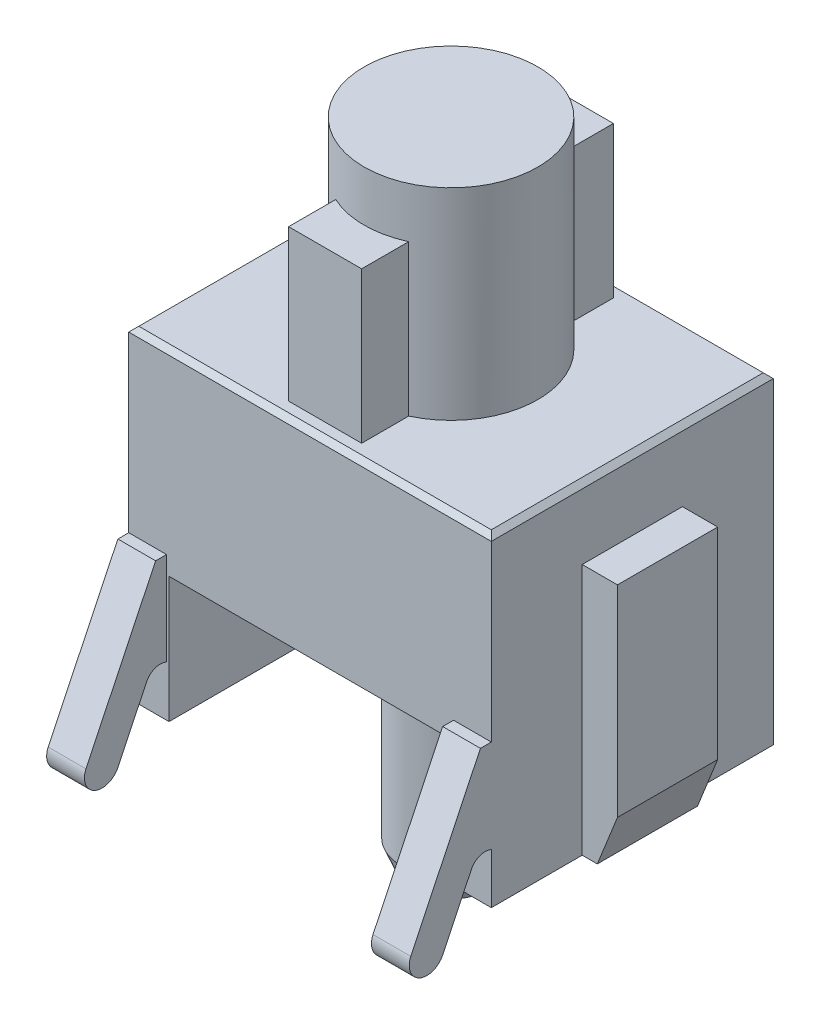
SolidWorks part; units mm, degrees
ref_plane "Front Plane" through (0, 0, 0) normal (0, 0, 1) x (1, 0, 0)
ref_plane "Top Plane" through (0, 0, 0) normal (0, 1, 0) x (1, 0, 0)
ref_plane "Right Plane" through (0, 0, 0) normal (1, 0, 0) x (0, 0, -1)
sketch "Sketch1" plane through (0, 0, 0) normal (0, 1, 0) x (1, 0, 0)
  line L1 (-3.6, -2.8) -> (3.6, -2.8)
  line L2 (-3.6, -2.8) -> (-3.6, 2.8)
  line L3 (-3.6, 2.8) -> (3.6, 2.8)
  line L4 (3.6, -2.8) -> (3.6, 2.8)
  line L5 (-3.6, -2.8) -> (3.6, 2.8) construction
  line L6 (-3.6, 2.8) -> (3.6, -2.8) construction
  point P0 (0, 0)
  dimension "D1" = 7.2
  dimension "D2" = 5.6
extrude "Body" add sketch "Sketch1" along normal blind 6.4
chamfer "Body Chamfer" distance 0.1 angle 45 4 edges at (0, 6.4, 2.8) (3.6, 6.4, 0) (0, 6.4, -2.8) (-3.6, 6.4, 0)
sketch "Sketch2" plane through (0, 6.4, 0) normal (0, 1, 0) x (1, 0, 0)
  circle A0 centre (0, 0) radius 1.725
  dimension "D1" = 3.45
extrude "Mount" add sketch "Sketch2" along normal blind 4
sketch "Sketch3" plane through (0, 6.4, 0) normal (0, 1, 0) x (1, 0, 0)
  line L1 (-0.725, -2.5) -> (0.725, -2.5)
  line L2 (-0.725, -2.5) -> (-0.725, 2.5)
  line L3 (-0.725, 2.5) -> (0.725, 2.5)
  line L4 (0.725, -2.5) -> (0.725, 2.5)
  line L5 (-0.725, -2.5) -> (0.725, 2.5) construction
  line L6 (-0.725, 2.5) -> (0.725, -2.5) construction
  point P0 (0, 0)
  dimension "D1" = 5
  dimension "D2" = 1.45
extrude "Mount Rails" add sketch "Sketch3" along normal blind 3
sketch "Sketch4" plane through (0, 0, 0) normal (0, -1, 0) x (1, 0, 0)
  circle A0 centre (0, 0) radius 2.25
  dimension "D1" = 4.5
extrude "Body Cut 1" cut sketch "Sketch4" against normal blind 4.8
sketch "Sketch5" plane through (0, 0, 0) normal (0, -1, 0) x (1, 0, 0)
  line L0 (-3.6, 2.8) -> (3.6, 2.8) construction
  line L1 (-2.8, -2.8) -> (2.8, -2.8)
  line L2 (-2.8, -2.8) -> (-2.8, 2.8)
  line L3 (-2.8, 2.8) -> (2.8, 2.8)
  line L4 (2.8, -2.8) -> (2.8, 2.8)
  line L5 (-2.8, -2.8) -> (2.8, 2.8) construction
  line L6 (-2.8, 2.8) -> (2.8, -2.8) construction
  point P0 (0, 0)
  dimension "D1" = 5.6
extrude "Body Cut 2" cut sketch "Sketch5" against normal blind 2.5
sketch "Sketch6" plane through (0, 4.8, 0) normal (0, -1, 0) x (1, 0, 0)
  circle A0 centre (0, 0) radius 0.975
  dimension "D1" = 1.95
extrude "Pole" add sketch "Sketch6" along normal blind 7.3
chamfer "Pole Chamfer" distance 0.5 distance2 0.2 1 edges at (0, -2.5, -0.975) first distance on face at (0, -2.5, -0.975)
sketch "Sketch7" plane through (3.6, 0, 0) normal (1, 0, 0) x (0, 0, -1)
  line L1 (-0.995, 5) -> (0.995, 5)
  line L2 (-0.995, 5) -> (-0.995, 0)
  line L3 (-0.995, 0) -> (0.995, 0)
  line L4 (0.995, 5) -> (0.995, 0)
  line L5 (-0.995, 5) -> (0.995, 0) construction
  line L6 (-0.995, 0) -> (0.995, 5) construction
  line L7 (-2.8, 0) -> (2.8, 0) construction
  point P0 (0, 2.5)
  dimension "D1" = 1.99
  dimension "D3" = 5
extrude "Right Rail" add sketch "Sketch7" along normal blind 0.7
mirror "Rail Mirror" about plane through (0, 0, 0) normal (1, 0, 0) of "Right Rail"
chamfer "Right Rail Chamfer" distance 0.4 distance2 1 1 edges at (4.3, 0, 0) first distance on face at (3.575, 0, 0)
chamfer "Left Rail Chamfer" distance 1 distance2 0.4 1 edges at (-4.3, 0, 0) first distance on face at (-4.3, 2.5, 0)
sketch "Sketch8" plane through (3.6, 0, 0) normal (1, 0, 0) x (0, 0, -1)
  line L0 (-3.0162, 2.8492) -> (-4.4, -0.0362)
  line L5 (-3.0162, 2.8492) -> (-2.8, 2.8492)
  line L7 (-3.76, -0.3196) -> (-3.1978, 0.8525)
  line L8 (-2.8, 1) -> (-2.8, 2.8492)
  line L9 (-2.8, 0) -> (-0.995, 0) construction
  line L10 (-2.8, 6.3) -> (-2.8, 0) construction
  line L12 (-4.4, -0.0362) -> (-4.08, -0.1779) construction
  line L13 (-4.08, -0.1779) -> (-3.76, -0.3196) construction
  line L14 (-3.1978, 0.8525) -> (-2.9252, 0.7274) construction
  line L15 (-2.9252, 0.7274) -> (-2.8, 1) construction
  arc A0 (-3.1978, 0.8525) -> (-2.8, 1) centre (-2.9252, 0.7274) cw
  arc A1 (-4.4, -0.0362) -> (-3.76, -0.3196) centre (-4.08, -0.1779) ccw
  dimension "D6" = 0.35
  dimension "D7" = 0.3
  dimension "D1" = 1
  dimension "D2" = 1.6
  dimension "D3" = 3.2
  dimension "D4" = 1.3
extrude "Right Leg" add sketch "Sketch8" against normal blind 0.75
mirror "Leg Mirror" about plane through (0, 0, 0) normal (1, 0, 0) of "Right Leg"
